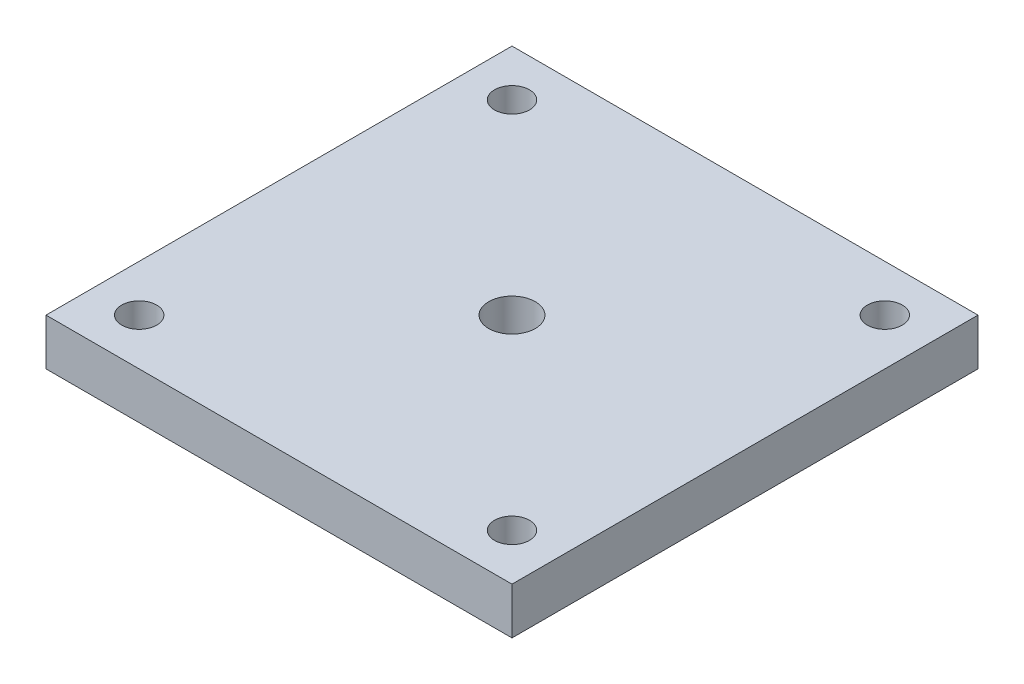
SolidWorks part; units mm, degrees
ref_plane "Front Plane" through (0, 0, 0) normal (0, 0, 1) x (1, 0, 0)
ref_plane "Top Plane" through (0, 0, 0) normal (0, 1, 0) x (1, 0, 0)
ref_plane "Right Plane" through (0, 0, 0) normal (1, 0, 0) x (0, 0, -1)
sketch "Sketch1" plane through (0, 0, 0) normal (0, 1, 0) x (1, 0, 0)
  line L1 (63.5, -63.5) -> (-63.5, -63.5)
  line L2 (63.5, -63.5) -> (63.5, 63.5)
  line L3 (63.5, 63.5) -> (-63.5, 63.5)
  line L4 (-63.5, -63.5) -> (-63.5, 63.5)
  line L5 (63.5, -63.5) -> (-63.5, 63.5) construction
  line L6 (63.5, 63.5) -> (-63.5, -63.5) construction
  circle A0 centre (0, 0) radius 6.35
  point P0 (0, 0)
  dimension "D3" = 12.7
  dimension "D1" = 127
  dimension "D2" = 127
extrude "Boss-Extrude1" add sketch "Sketch1" along normal blind 12.7
sketch "Sketch2" plane through (0, 12.7, 0) normal (0, 1, 0) x (1, 0, 0)
  line L0 (-63.5, 63.5) -> (-63.5, -63.5) construction
  line L1 (-50.8, 50.8) -> (50.8, 50.8) construction
  line L2 (-50.8, 50.8) -> (-50.8, -50.8) construction
  line L3 (-50.8, -50.8) -> (50.8, -50.8) construction
  line L4 (50.8, 50.8) -> (50.8, -50.8) construction
  line L5 (63.5, 63.5) -> (-63.5, 63.5) construction
  circle A0 centre (-50.8, 50.8) radius 4.7625
  circle A1 centre (-50.8, -50.8) radius 4.7625
  circle A2 centre (50.8, -50.8) radius 4.7625
  circle A3 centre (50.8, 50.8) radius 4.7625
  point P12 (-50.8, 0)
  point P14 (0, 50.8)
  dimension "D1" = 9.525
  dimension "D3" = 12.7
  dimension "D2" = 12.7
extrude "Cut-Extrude1" cut sketch "Sketch2" against normal through all
